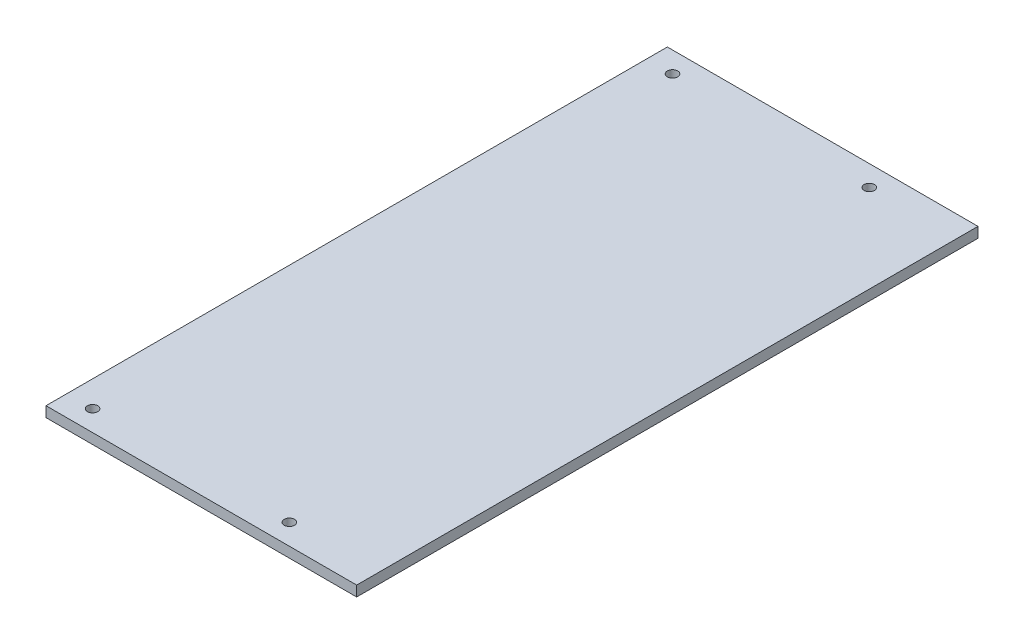
SolidWorks part; units mm, degrees
ref_plane "Front Plane" through (0, 0, 0) normal (0, 0, 1) x (1, 0, 0)
ref_plane "Top Plane" through (0, 0, 0) normal (0, 1, 0) x (1, 0, 0)
ref_plane "Right Plane" through (0, 0, 0) normal (1, 0, 0) x (0, 0, -1)
sketch "Sketch1" plane through (0, 0, 0) normal (0, 1, 0) x (1, 0, 0)
  line L1 (-45, -90) -> (45, -90)
  line L2 (-45, -90) -> (-45, 90)
  line L3 (-45, 90) -> (45, 90)
  line L4 (45, -90) -> (45, 90)
  line L5 (-45, -90) -> (45, 90) construction
  line L6 (-45, 90) -> (45, -90) construction
  circle A0 centre (19.5, -84) radius 1.5 construction
  circle A1 centre (-37.5, -84) radius 1.5 construction
  circle A2 centre (19.5, 84) radius 1.5 construction
  circle A3 centre (-37.5, 84) radius 1.5 construction
  circle A4 centre (19.5, -84) radius 1.5
  circle A5 centre (-37.5, -84) radius 1.5
  circle A6 centre (19.5, 84) radius 1.5
  circle A7 centre (-37.5, 84) radius 1.5
  point P0 (0, 0)
  dimension "D1" = 90
  dimension "D2" = 180
extrude "Boss-Extrude1" add sketch "Sketch1" along normal blind 3
